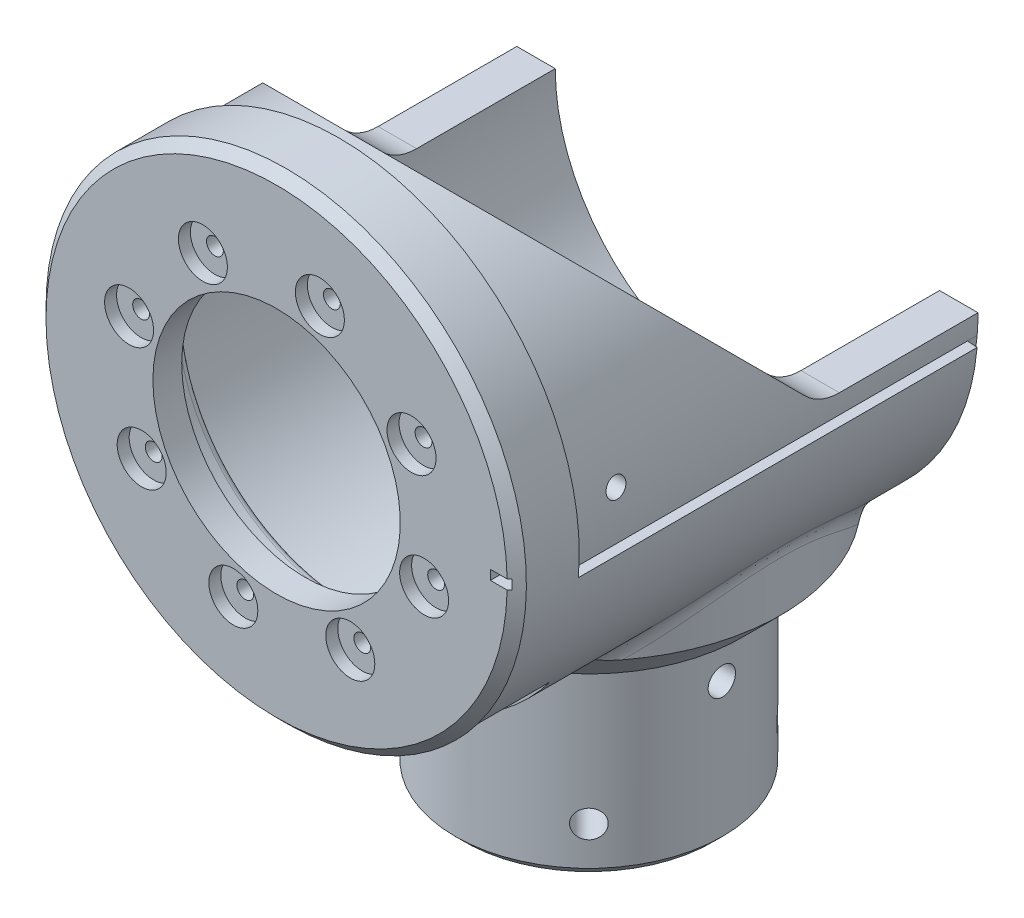
SolidWorks part; units mm, degrees
material "PETG"
ref_plane "Спереди" through (0, 0, 0) normal (0, 0, 1) x (1, 0, 0)
ref_plane "Сверху" through (0, 0, 0) normal (0, 1, 0) x (1, 0, 0)
ref_plane "Справа" through (0, 0, 0) normal (1, 0, 0) x (0, 0, -1)
sketch "Эскиз6" plane through (0, 0, 0) normal (0, 0, 1) x (1, 0, 0)
  circle A0 centre (0, 50) radius 50
  dimension "D1" = 100
extrude "Бобышка-Вытянуть4" add sketch "Эскиз6" along normal mid plane 130
sketch "Эскиз7" plane through (0, 0, 0) normal (0, 1, 0) x (1, 0, 0)
  circle A0 centre (0, 0) radius 40
  dimension "D1" = 80
extrude "Бобышка-Вытянуть5" add sketch "Эскиз7" along normal blind 30
sketch "Эскиз9" plane through (0, 0, 0) normal (1, 0, 0) x (0, 0, -1)
  line L0 (65, 50) -> (0, 50)
  line L1 (65, 0) -> (65, 100) construction
  line L2 (0, 50) -> (-50, 100)
  line L3 (65, 100) -> (-65, 100) construction
  line L4 (-65, 100) -> (-65, 0) construction
  line L5 (-50, 100) -> (65, 100)
  line L6 (65, 100) -> (65, 50)
  dimension "D1" = 45
  dimension "D2" = 15
extrude "Вырез-Вытянуть1" cut sketch "Эскиз9" against normal through all both and the other way through all
sketch "Эскиз20" plane through (0, 0, 0) normal (0, -1, 0) x (1, 0, 0)
  circle A0 centre (0, 0) radius 27.825
extrude "Бобышка-Вытянуть8" add sketch "Эскиз20" along normal blind 40
chamfer "Фаска2" distance 8 angle 45 2 edges at (40, 0, 0) (-40, 0, 0)
chamfer "Фаска3" distance 2 angle 45 2 edges at (50, 50, 65) (0, -40, -27.825)
sketch "Эскиз16" plane through (0, 0, -65) normal (0, 0, -1) x (-1, 0, 0)
  line L2 (50, 50) -> (-50, 50)
  line L4 (50, 50) -> (-50, 50)
  arc A3 (-50, 50) -> (50, 50) centre (0, 50) ccw
  arc A5 (-50, 50) -> (50, 50) centre (0, 50) ccw
  dimension "D1" = 0
extrude "Вырез-Вытянуть7" cut sketch "Эскиз16" against normal blind 32
sketch "Эскиз18" plane through (0, 0, 52) normal (0, 0, -1) x (-1, 0, 0)
  line L0 (47.8173, 45.8165) -> (49.8097, 45.6422) construction
  line L1 (-49.8097, 45.6422) -> (-47.8173, 45.8165) construction
  line L2 (47.8173, 45.8165) -> (49.8097, 45.6422)
  line L3 (-49.8097, 45.6422) -> (-47.8173, 45.8165)
  arc A0 (49.8097, 45.6422) -> (-49.8097, 45.6422) centre (0, 50) ccw
  arc A1 (47.8173, 45.8165) -> (-47.8173, 45.8165) centre (0, 50) ccw
extrude "Вырез-Вытянуть9" cut sketch "Эскиз18" along normal through all
fillet "Скругление1" radius 10 1 edges at (0, 50, 0)
fillet "Скругление2" radius 5 2 edges at (39.8638, 19.8193, -3.2978) (-39.9691, 19.9589, 1.5713)
ref_axis "Ось2" through (0, -38, 0) along (0, 1, 0)
ref_plane "Плоскость2" through (0, 0, 0) normal (0.7071, 0, -0.7071) x (0, 1, 0)
sketch "Эскиз21" plane through (-23.75, 23.75, 0) normal (0.7071, -0.7071, 0) x (0, 0, 1)
  line L0 (65, -35.3553) -> (37.174, -35.3553) construction
  line L1 (65, -83.3553) -> (65, 12.6447) construction
  line L2 (63, 14.6447) -> (63, -85.3553) construction
  line L3 (63, -28.3553) -> (48, -28.3553)
  line L4 (63, -28.3553) -> (63, -42.3553)
  line L5 (63, -42.3553) -> (48, -42.3553)
  line L6 (48, -28.3553) -> (48, -42.3553)
  line L7 (63, -28.3553) -> (48, -42.3553) construction
  line L8 (63, -42.3553) -> (48, -28.3553) construction
  point P4 (55.5, -35.3553)
  dimension "D1" = 14
  dimension "D2" = 15
extrude "Вырез-Вытянуть10" cut sketch "Эскиз21" along normal through all from offset 47
sketch "Эскиз23" plane through (9.484, -9.484, 0) normal (0.7071, -0.7071, 0) x (0, 0, -1)
  line L0 (-63, 35.3553) -> (-48, 35.3553) construction
  line L1 (-63, 42.3553) -> (-63, 28.3553) construction
  line L2 (-48, 28.3553) -> (-48, 42.3553) construction
  circle A0 centre (-53, 38.3553) radius 1.1
  dimension "D1" = 2.2
  dimension "D2" = 6
  dimension "D3" = 10
extrude "Вырез-Вытянуть11" cut sketch "Эскиз23" against normal blind 3
sketch "Эскиз24" plane through (9.484, -9.484, 0) normal (0.7071, -0.7071, 0) x (0, 0, -1)
  line L0 (-53, 32.3553) -> (-53, 38.3553) construction
  circle A0 centre (-53, 32.3553) radius 2.05
  dimension "D1" = 6
  dimension "D2" = 4.1
extrude "Вырез-Вытянуть12" cut sketch "Эскиз24" against normal blind 6.5
sketch "Эскиз25" plane through (0, 0, 65) normal (0, 0, 1) x (1, 0, 0)
  line L0 (46.5, 50) -> (0, 50) construction
  line L1 (44.5, 51) -> (48.5, 51)
  line L2 (44.5, 51) -> (44.5, 49)
  line L3 (44.5, 49) -> (48.5, 49)
  line L4 (48.5, 51) -> (48.5, 49)
  line L5 (44.5, 51) -> (48.5, 49) construction
  line L6 (44.5, 49) -> (48.5, 51) construction
  arc A0 (39.9569, 19.9426) -> (30.0574, 10.0431) centre (0, 50) ccw construction
  arc A1 (39.9569, 19.9426) -> (30.0574, 10.0431) centre (0, 50) ccw construction
  point P0 (46.5, 50)
  dimension "D1" = 2
  dimension "D2" = 4
  dimension "D3" = 48.5
extrude "Вырез-Вытянуть13" cut sketch "Эскиз25" against normal blind 5
sketch "Эскиз26" plane through (0, 0, 0) normal (1, 0, 0) x (0, 0, -1)
  line L0 (-52, 45.6422) -> (-52, 100) construction
  line L1 (-52, 45.8165) -> (33, 45.8165) construction
  circle A0 centre (-42, 55.8165) radius 2.05
  dimension "D1" = 4.1
  dimension "D2" = 10
  dimension "D3" = 10
extrude "Вырез-Вытянуть14" cut sketch "Эскиз26" against normal through all both and the other way through all
sketch "Эскиз27" plane through (0, 0, -34) normal (0, 0, -1) x (-1, 0, 0)
  line L0 (0, 50) -> (0, 4.5) construction
  circle A0 centre (0, 50) radius 45.5 construction
  circle A1 centre (0, 50) radius 39 construction
  circle A2 centre (0, 50) radius 44 construction
  circle A3 centre (-25, 13.7923) radius 2.05
  circle A4 centre (25, 13.7923) radius 2.05
  circle A5 centre (-42.5727, 38.8842) radius 2.05
  circle A6 centre (42.5727, 38.8842) radius 2.05
  dimension "D1" = 78
  dimension "D2" = 91
  dimension "D3" = 88
  dimension "D4" = 4.1
  dimension "D5" = 50
  dimension "D6" = 4.1
  dimension "D7" = 4.1
extrude "Вырез-Вытянуть15" cut sketch "Эскиз27" against normal blind 7
sketch "Эскиз28" plane through (0, 0, 0) normal (0, 0, 1) x (1, 0, 0)
  circle A0 centre (0, -10) radius 2.85
  dimension "D1" = 5.7
  dimension "D2" = 10
extrude "Вырез-Вытянуть16" cut sketch "Эскиз28" against normal blind 15 from offset 28
sketch "Эскиз29" plane through (0, 0, 0) normal (0.7071, 0, -0.7071) x (-0.7071, 0, -0.7071)
  line L0 (-27.825, -40) -> (27.825, -40) construction
  circle A0 centre (0, -30) radius 2.85
  dimension "D1" = 5.7
  dimension "D2" = 10
extrude "Вырез-Вытянуть17" cut sketch "Эскиз29" against normal blind 15 from offset 28
pattern_circular "Круговой массив2" count 4 over 360 about axis through (0, -40, 0) along (0, 1, 0) of "Вырез-Вытянуть16", "Вырез-Вытянуть17" reverse direction yes
sketch "Sketch2" plane through (0, 0, 42.5) normal (0, 0, -1) x (-1, 0, 0)
  circle A0 centre (0, 50) radius 25.75
extrude "Cut-Extrude1" cut sketch "Sketch2" against normal through all
sketch "Sketch3" plane through (0, 0, 42.5) normal (0, 0, -1) x (-1, 0, 0)
  circle A0 centre (0, 50) radius 40
  dimension "D1" = 80
extrude "Cut-Extrude2" cut sketch "Sketch3" along normal through all and the other way offset from surface 16 other way up to face at (-25.75, 50, 65)
sketch "Sketch4" plane through (0, 0, 43.5) normal (0, 0, -1) x (-1, 0, 0)
  circle A0 centre (0, 50) radius 35.1
  dimension "D1" = 70.2
extrude "Cut-Extrude3" cut sketch "Sketch4" against normal offset from surface (15.5 mm away) 6 up to face at (-25.75, 50, 65)
sketch "Sketch5" plane through (0, 0, 65) normal (0, 0, 1) x (1, 0, 0)
  circle A0 centre (-15.342, 78.0824) radius 1.75
  circle A1 centre (0, 50) radius 25.75 construction
  circle A2 centre (9.0089, 80.7057) radius 1.75
  circle A3 centre (28.0824, 65.342) radius 1.75
  circle A4 centre (30.7057, 40.9911) radius 1.75
  circle A5 centre (15.342, 21.9176) radius 1.75
  circle A6 centre (-9.0089, 19.2943) radius 1.75
  circle A7 centre (-28.0824, 34.658) radius 1.75
  circle A8 centre (-30.7057, 59.0089) radius 1.75
  point P21 (0, 50)
  point P28 (0, 50)
  dimension "D1" = 32
  dimension "D3" = 8
  dimension "D2" = 3.5
extrude "Cut-Extrude4" cut sketch "Sketch5" against normal blind 14
sketch "Sketch6" plane through (0, 0, 65) normal (0, 0, 1) x (1, 0, 0)
  circle A1 centre (-15.342, 78.0824) radius 5.1
  circle A12 centre (9.0089, 80.7057) radius 5.1
  circle A13 centre (28.0824, 65.342) radius 5.1
  circle A14 centre (30.7057, 40.9911) radius 5.1
  circle A15 centre (15.342, 21.9176) radius 5.1
  circle A16 centre (-9.0089, 19.2943) radius 5.1
  circle A17 centre (-28.0824, 34.658) radius 5.1
  circle A18 centre (-30.7057, 59.0089) radius 5.1
  point P19 (0, 50)
  dimension "D1" = 8
extrude "Cut-Extrude5" cut sketch "Sketch6" against normal blind 2.5
sketch "Sketch7" plane through (0, -40, 0) normal (0, -1, 0) x (1, 0, 0)
  circle A0 centre (0, 0) radius 16
  dimension "D1" = 32
extrude "Cut-Extrude6" cut sketch "Sketch7" against normal up to next
sketch "Sketch8" plane through (0, 0, -33) normal (0, 0, -1) x (1, 0, 0)
  line L0 (-49.8097, -45.6422) -> (-47.8173, -45.8165)
  line L1 (47.8173, -45.8165) -> (49.8097, -45.6422)
  arc A1 (-47.8173, -45.8165) -> (47.8173, -45.8165) centre (0, -49.5902) cw
  arc A2 (49.8097, -45.6422) -> (-49.8097, -45.6422) centre (0, -49.3789) ccw
extrude "Cut-Extrude11" cut sketch "Sketch8" against normal blind 2
fillet "Fillet1" radius 2 2 edges at (-2.3199, 10.0673, 15.8309) (0, -40, -16)
fillet "Fillet3" radius 1.5 1 edges at (35.1, 50, 49)
